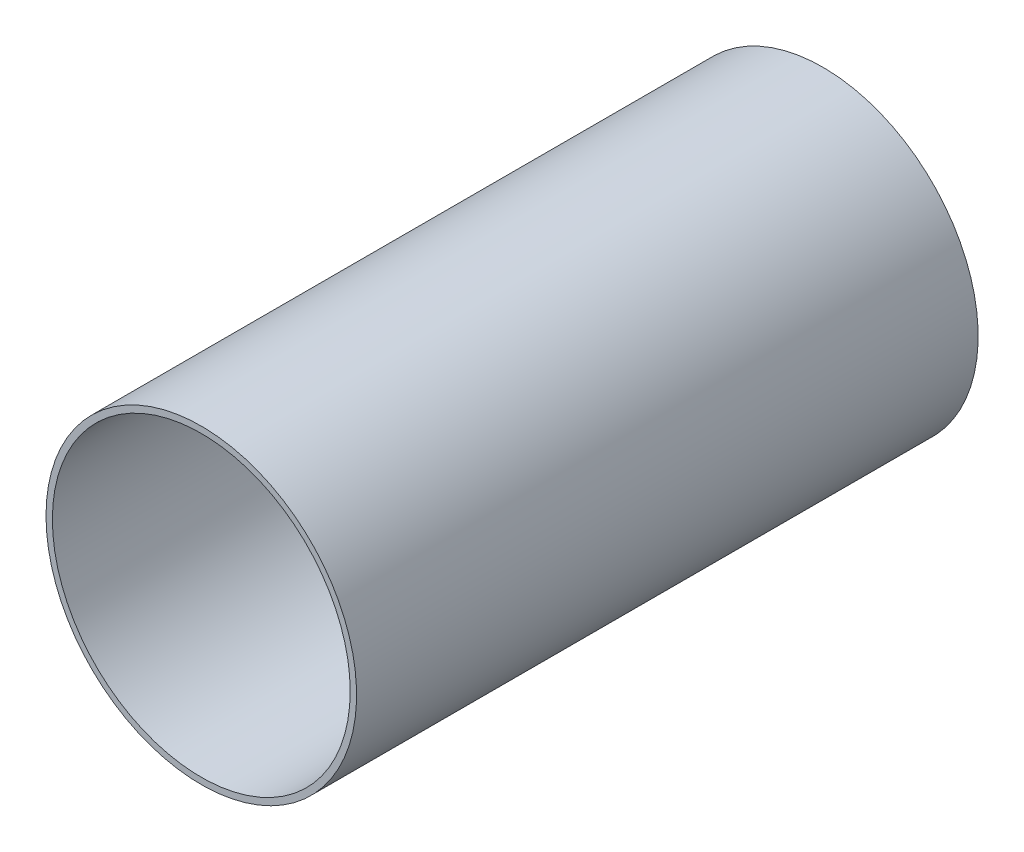
SolidWorks part; units mm, degrees
ref_plane "Front Plane" through (0, 0, 0) normal (0, 0, 1) x (1, 0, 0)
ref_plane "Top Plane" through (0, 0, 0) normal (0, 1, 0) x (1, 0, 0)
ref_plane "Right Plane" through (0, 0, 0) normal (1, 0, 0) x (0, 0, -1)
sketch "Sketch1" plane through (0, 0, 0) normal (0, 0, 1) x (1, 0, 0)
  circle A0 centre (0, 0) radius 38.0746
  circle A1 centre (0, 0) radius 36.5125
  dimension "D1" = 73.025
  dimension "D2" = 76.1492
extrude "Boss-Extrude1" add sketch "Sketch1" along normal mid plane 152.4
equation "\"AIRFRAME_OD\"= 3.091in"
equation "\"AIRFRAME_ID\"= 3.00in"
equation "\"FLAT_T\"= 0.125in"
equation "\"NOSE_EXP_L\"= 3.5in"
equation "\"NOSE_SHOULDER_L\"= 5in"
equation "\"MAIN_L\"= 30in"
equation "\"RECO_COUP_L\"= 6in"
equation "\"RECO_SWITCH_L\"= 1.5in"
equation "\"DROGUE_L\"= 14in"
equation "\"ATS_FORE_COUP_L\"= 4in"
equation "\"ATS_AFT_COUP_L\"= 2.5in"
equation "\"LOWER_L\"= 16in"
equation "\"FIN_N\"= 4"
equation "\"CR_AFT_X\"= 0.5in"
equation "\"CR_FORE_X\"= 6in"
equation "\"D1@Sketch1\"=\"COUPLER_ID\""
equation "\"D2@Sketch1\"=\"COUPLER_OD\""
equation "\"D1@Boss-Extrude1\"=\"RECO_COUP_L\""
equation "\"FIN_ROOT\"= 5in"
equation "\"FIN_X\"= 0.75in"
equation "\"MOTOR_OD\"= 2.25in"
equation "\"MOTOR_ID\"= 2.126in"
equation "\"COUPLER_OD\"= 2.998in"
equation "\"COUPLER_ID\"= 2.875in"
